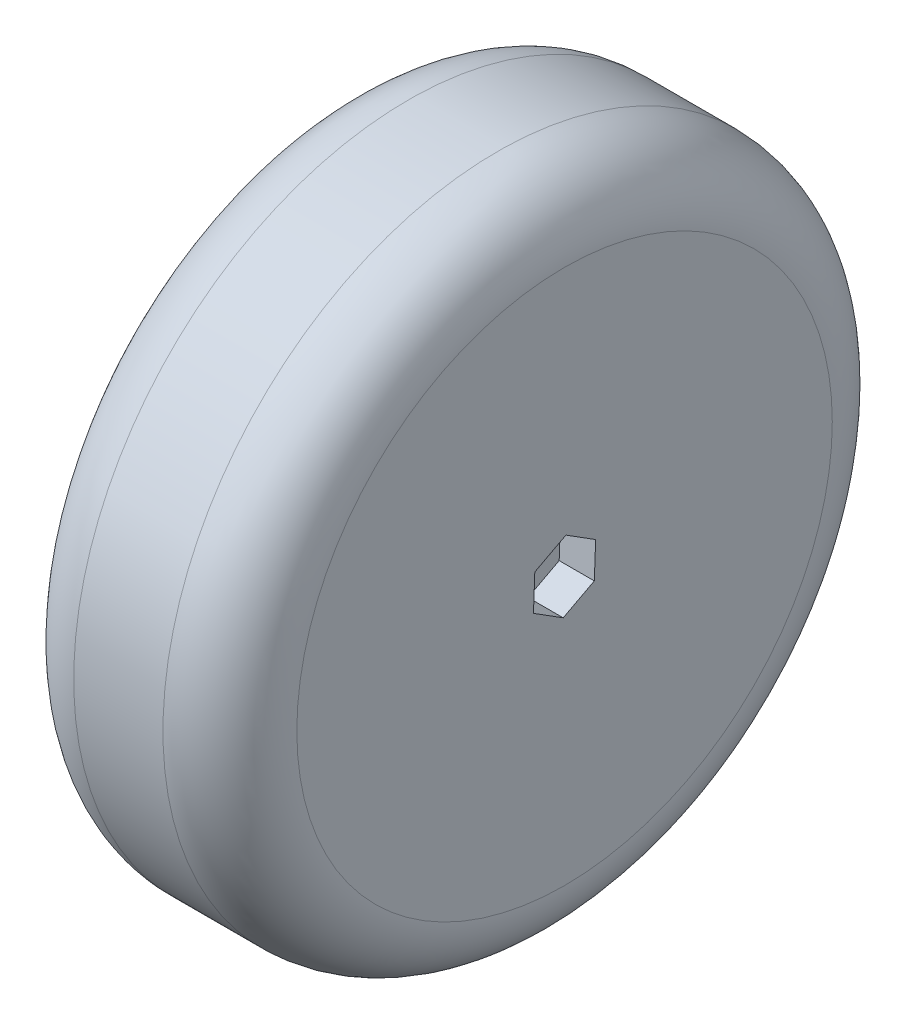
SolidWorks part; units mm, degrees
material "6063-T6"
ref_plane "Front Plane" through (0, 0, 0) normal (0, 0, 1) x (1, 0, 0)
ref_plane "Top Plane" through (0, 0, 0) normal (0, 1, 0) x (1, 0, 0)
ref_plane "Right Plane" through (0, 0, 0) normal (1, 0, 0) x (0, 0, -1)
sketch "Sketch2" plane through (0, 0, 0) normal (1, 0, 0) x (0, 0, -1)
  circle A0 centre (0, 0) radius 38.1
  dimension "D1" = 76.2
extrude "Boss-Extrude2" add sketch "Sketch2" along normal blind 25.4 contours A0
fillet "Fillet3" radius 7.62 1 edges at (25.4, 0, -38.1)
fillet "Fillet5" radius 7.62 1 edges at (0, 0, -38.1)
sketch "Sketch4" plane through (25.4, 0, 0) normal (1, 0, 0) x (0, 0, -1)
  circle A0 centre (0, 0) radius 1.7
extrude "Cut-Extrude1" cut sketch "Sketch4" against normal blind 25.4
sketch "Sketch5" plane through (25.4, 0, 0) normal (1, 0, 0) x (0, 0, -1)
  line L1 (-3.3873, 2.1327) -> (-3.5406, -1.8671)
  line L2 (-3.5406, -1.8671) -> (-0.1534, -3.9998)
  line L3 (-0.1534, -3.9998) -> (3.3873, -2.1327)
  line L4 (3.3873, -2.1327) -> (3.5406, 1.8671)
  line L5 (3.5406, 1.8671) -> (0.1534, 3.9998)
  line L6 (0.1534, 3.9998) -> (-3.3873, 2.1327)
  circle A0 centre (0, 0) radius 3.4665 construction
extrude "Cut-Extrude2" cut sketch "Sketch5" against normal blind 4
ref_axis "Axis1" through (-61.627, 0, 0) along (1, 0, 0)
ref_plane "Plane1" through (25.4, 0, 0) normal (1, 0, 0) x (0, 0, -1)
